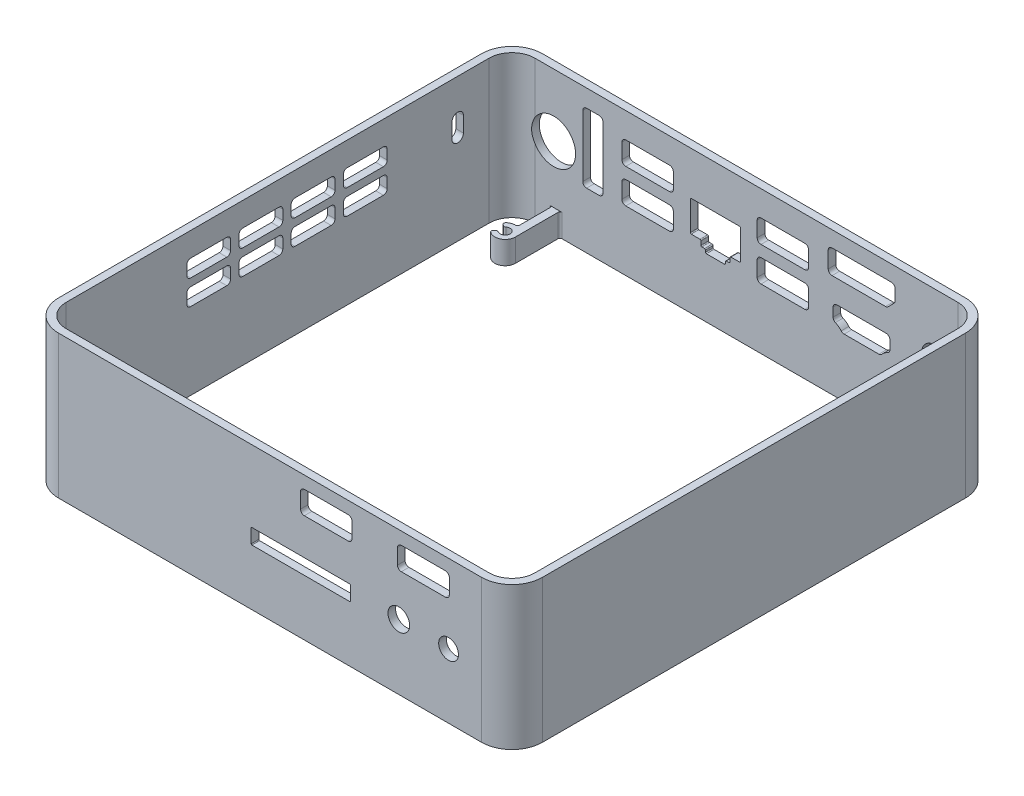
SolidWorks part; units mm, degrees
ref_plane "Front Plane" through (0, 0, 0) normal (0, 0, 1) x (1, 0, 0)
ref_plane "Top Plane" through (0, 0, 0) normal (0, 1, 0) x (1, 0, 0)
ref_plane "Right Plane" through (0, 0, 0) normal (1, 0, 0) x (0, 0, -1)
sketch "Sketch1" plane through (0, 0, 0) normal (0, 1, 0) x (1, 0, 0)
  line L0 (2, 8) -> (2, 119)
  line L1 (8, 0) -> (119, 0)
  line L2 (0, 8) -> (0, 119)
  line L3 (8, 127) -> (119, 127)
  line L4 (127, 8) -> (127, 119)
  line L5 (8, 125) -> (119, 125)
  line L6 (125, 8) -> (125, 119)
  line L7 (8, 2) -> (119, 2)
  arc A0 (119, 0) -> (127, 8) centre (119, 8) ccw
  arc A1 (8, 0) -> (0, 8) centre (8, 8) cw
  arc A2 (119, 127) -> (127, 119) centre (119, 119) cw
  arc A3 (0, 119) -> (8, 127) centre (8, 119) cw
  arc A4 (2, 119) -> (8, 125) centre (8, 119) cw
  arc A5 (119, 125) -> (125, 119) centre (119, 119) cw
  arc A6 (119, 2) -> (125, 8) centre (119, 8) ccw
  arc A7 (8, 2) -> (2, 8) centre (8, 8) cw
  point P9 (0, 0)
  dimension "D3" = 8
  dimension "D1" = 127
  dimension "D2" = 127
  dimension "D4" = 2
extrude "Boss-Extrude1" add sketch "Sketch1" along normal blind 37.5
sketch "Sketch12" plane through (0, 0, 0) normal (1, 0, 0) x (0, 0, -1)
  line L1 (40.65, 31.2) -> (50.15, 31.2)
  line L2 (39.65, 30.2) -> (39.65, 27.7)
  line L3 (40.65, 26.7) -> (50.15, 26.7)
  line L4 (51.15, 30.2) -> (51.15, 27.7)
  arc A0 (39.65, 27.7) -> (40.65, 26.7) centre (40.65, 27.7) ccw
  arc A1 (50.15, 26.7) -> (51.15, 27.7) centre (50.15, 27.7) ccw
  arc A2 (50.15, 31.2) -> (51.15, 30.2) centre (50.15, 30.2) cw
  arc A3 (40.65, 31.2) -> (39.65, 30.2) centre (40.65, 30.2) ccw
  dimension "D5" = 1
  dimension "D1" = 39.65
  dimension "D2" = 11.5
  dimension "D3" = 26.7
  dimension "D4" = 4.5
extrude "Cut-Extrude2" cut sketch "Sketch12" along normal up to next
pattern_linear "LPattern1" count 2 spacing 6.5 along (0, -1, 0) count 4 spacing 13.7 along (0, 0, -1) of "Cut-Extrude2"
sketch "Sketch18" plane through (0, 0, 0) normal (-1, 0, 0) x (0, 0, 1)
  line L0 (-110.75, 23.85) -> (-110.75, 27.85) construction
  line L1 (-112.25, 23.85) -> (-112.25, 27.85)
  line L2 (-109.25, 23.85) -> (-109.25, 27.85)
  line L3 (-119, 37.5) -> (-8, 37.5) construction
  line L4 (-127, 37.5) -> (-127, 0) construction
  arc A0 (-112.25, 23.85) -> (-109.25, 23.85) centre (-110.75, 23.85) ccw
  arc A1 (-109.25, 27.85) -> (-112.25, 27.85) centre (-110.75, 27.85) ccw
  point P2 (-110.75, 25.85)
  dimension "D2" = 1.5
  dimension "D1" = 4
  dimension "D3" = 9.65
  dimension "D4" = 16.25
extrude "Cut-Extrude8" cut sketch "Sketch18" against normal up to next
sketch "Sketch15" plane through (0, 0, 0) normal (0, 0, 1) x (1, 0, 0)
  line L0 (0, 37.5) -> (0, 0) construction
  line L1 (84.45, 18.7) -> (58.75, 18.7)
  line L2 (84.65, 18.5) -> (84.65, 14.9)
  line L3 (84.45, 14.7) -> (58.75, 14.7)
  line L4 (58.55, 18.5) -> (58.55, 14.9)
  line L5 (72.5, 34.25) -> (84, 34.25)
  line L6 (71.5, 33.25) -> (71.5, 29.25)
  line L7 (72.5, 28.25) -> (84, 28.25)
  line L8 (85, 33.25) -> (85, 29.25)
  line L9 (97.95, 34.25) -> (109.55, 34.25)
  line L10 (96.95, 33.25) -> (96.95, 29.25)
  line L11 (97.95, 28.25) -> (109.55, 28.25)
  line L12 (110.55, 33.25) -> (110.55, 29.25)
  line L14 (8, 0) -> (119, 0) construction
  line L15 (8, 37.5) -> (119, 37.5) construction
  circle A0 centre (97.3, 17.1) radius 2.85
  circle A1 centre (110.35, 16.9) radius 2.6
  arc A2 (84, 28.25) -> (85, 29.25) centre (84, 29.25) ccw
  arc A3 (84, 34.25) -> (85, 33.25) centre (84, 33.25) cw
  arc A4 (72.5, 34.25) -> (71.5, 33.25) centre (72.5, 33.25) ccw
  arc A5 (71.5, 29.25) -> (72.5, 28.25) centre (72.5, 29.25) ccw
  arc A6 (84.65, 14.9) -> (84.45, 14.7) centre (84.45, 14.9) cw
  arc A7 (84.45, 18.7) -> (84.65, 18.5) centre (84.45, 18.5) cw
  arc A8 (58.75, 14.7) -> (58.55, 14.9) centre (58.75, 14.9) cw
  arc A9 (58.75, 18.7) -> (58.55, 18.5) centre (58.75, 18.5) ccw
  arc A10 (96.95, 29.25) -> (97.95, 28.25) centre (97.95, 29.25) ccw
  arc A11 (109.55, 28.25) -> (110.55, 29.25) centre (109.55, 29.25) ccw
  arc A12 (109.55, 34.25) -> (110.55, 33.25) centre (109.55, 33.25) cw
  arc A13 (97.95, 34.25) -> (96.95, 33.25) centre (97.95, 33.25) ccw
  dimension "D13" = 5.7
  dimension "D14" = 5.2
  dimension "D15" = 1
  dimension "D3" = 1
  dimension "D2" = 0.2
  dimension "D4" = 13.6
  dimension "D5" = 13.5
  dimension "D6" = 6
  dimension "D7" = 6
  dimension "D8" = 26.1
  dimension "D9" = 4
  dimension "D10" = 58.55
  dimension "D11" = 71.5
  dimension "D12" = 96.95
  dimension "D16" = 97.3
  dimension "D17" = 110.35
  dimension "D18" = 16.9
  dimension "D19" = 17.1
  dimension "D20" = 14.7
  dimension "D21" = 3.25
  dimension "D22" = 3.25
extrude "Cut-Extrude5" cut sketch "Sketch15" against normal blind 2
sketch "Sketch16" plane through (0, 0, -127) normal (0, 0, -1) x (-1, 0, 0)
  line L0 (-100.162, 21.0556) -> (-87.262, 21.0556)
  line L1 (-86.262, 20.0556) -> (-86.262, 17.7485)
  line L2 (-89.1527, 15.3556) -> (-98.2712, 15.3556)
  line L3 (-101.162, 17.7485) -> (-101.162, 20.0556)
  line L4 (-101.5483, 33.3493) -> (-85.9787, 33.3493)
  line L5 (-78.8419, 30.8312) -> (-67.3419, 30.8312)
  line L6 (-79.8419, 29.8312) -> (-79.8419, 25.8312)
  line L7 (-78.8419, 24.8312) -> (-67.3419, 24.8312)
  line L8 (-66.3419, 29.8312) -> (-66.3419, 25.8312)
  line L9 (-24.8661, 32.9015) -> (-21.5749, 32.9015)
  line L10 (-25.8661, 31.9015) -> (-25.8661, 15.7374)
  line L11 (-24.8661, 14.7374) -> (-21.5749, 14.7374)
  line L12 (-20.5749, 31.9015) -> (-20.5749, 15.7374)
  line L13 (-84.9787, 32.3493) -> (-84.9787, 28.0682)
  line L14 (-85.9787, 27.0682) -> (-100.024, 27.0682)
  line L15 (-100.7372, 27.3673) -> (-102.2616, 28.9183)
  line L16 (-102.5483, 29.6193) -> (-102.5483, 32.3493)
  line L17 (-61.736, 26.1367) -> (-49.037, 26.1367)
  line L18 (-48.787, 25.8867) -> (-48.787, 18.2544)
  line L19 (-49.037, 18.0044) -> (-51.332, 18.0044)
  line L20 (-51.582, 17.7544) -> (-51.582, 16.7547)
  line L21 (-51.832, 16.5047) -> (-52.5205, 16.5047)
  line L22 (-52.7705, 16.2547) -> (-52.7705, 15.7891)
  line L23 (-53.0205, 15.5391) -> (-57.7525, 15.5391)
  line L24 (-58.0025, 15.7891) -> (-58.0025, 16.2547)
  line L25 (-58.2525, 16.5047) -> (-58.941, 16.5047)
  line L26 (-59.191, 16.7547) -> (-59.191, 17.7544)
  line L27 (-59.441, 18.0044) -> (-61.736, 18.0044)
  line L28 (-61.986, 18.2544) -> (-61.986, 25.8867)
  circle A0 centre (-113.0051, 21.3213) radius 3.5
  arc A1 (-86.866, 16.8303) -> (-88.3931, 15.7052) centre (-85.2027, 12.9737) ccw
  arc A2 (-99.0308, 15.7052) -> (-100.558, 16.8303) centre (-102.2212, 12.9737) ccw
  circle A3 centre (-12.946, 21.0556) radius 5.75
  arc A4 (-21.5749, 14.7374) -> (-20.5749, 15.7374) centre (-21.5749, 15.7374) ccw
  arc A5 (-25.8661, 15.7374) -> (-24.8661, 14.7374) centre (-24.8661, 15.7374) ccw
  arc A6 (-24.8661, 32.9015) -> (-25.8661, 31.9015) centre (-24.8661, 31.9015) ccw
  arc A7 (-67.3419, 30.8312) -> (-66.3419, 29.8312) centre (-67.3419, 29.8312) cw
  arc A8 (-67.3419, 24.8312) -> (-66.3419, 25.8312) centre (-67.3419, 25.8312) ccw
  arc A9 (-79.8419, 25.8312) -> (-78.8419, 24.8312) centre (-78.8419, 25.8312) ccw
  arc A10 (-78.8419, 30.8312) -> (-79.8419, 29.8312) centre (-78.8419, 29.8312) ccw
  arc A11 (-100.558, 16.8303) -> (-101.162, 17.7485) centre (-100.162, 17.7485) cw
  arc A12 (-98.2712, 15.3556) -> (-99.0308, 15.7052) centre (-98.2712, 16.3556) cw
  arc A13 (-88.3931, 15.7052) -> (-89.1527, 15.3556) centre (-89.1527, 16.3556) cw
  arc A14 (-86.262, 17.7485) -> (-86.866, 16.8303) centre (-87.262, 17.7485) cw
  arc A15 (-87.262, 21.0556) -> (-86.262, 20.0556) centre (-87.262, 20.0556) cw
  arc A16 (-100.162, 21.0556) -> (-101.162, 20.0556) centre (-100.162, 20.0556) ccw
  arc A17 (-21.5749, 32.9015) -> (-20.5749, 31.9015) centre (-21.5749, 31.9015) cw
  arc A18 (-100.024, 27.0682) -> (-100.7372, 27.3673) centre (-100.024, 28.0682) cw
  arc A19 (-84.9787, 28.0682) -> (-85.9787, 27.0682) centre (-85.9787, 28.0682) cw
  arc A20 (-85.9787, 33.3493) -> (-84.9787, 32.3493) centre (-85.9787, 32.3493) cw
  arc A21 (-101.5483, 33.3493) -> (-102.5483, 32.3493) centre (-101.5483, 32.3493) ccw
  arc A22 (-102.2616, 28.9183) -> (-102.5483, 29.6193) centre (-101.5483, 29.6193) cw
  arc A23 (-61.736, 18.0044) -> (-61.986, 18.2544) centre (-61.736, 18.2544) cw
  arc A24 (-59.191, 17.7544) -> (-59.441, 18.0044) centre (-59.441, 17.7544) ccw
  arc A25 (-58.941, 16.5047) -> (-59.191, 16.7547) centre (-58.941, 16.7547) cw
  arc A26 (-58.0025, 16.2547) -> (-58.2525, 16.5047) centre (-58.2525, 16.2547) ccw
  arc A27 (-57.7525, 15.5391) -> (-58.0025, 15.7891) centre (-57.7525, 15.7891) cw
  arc A28 (-52.7705, 15.7891) -> (-53.0205, 15.5391) centre (-53.0205, 15.7891) cw
  arc A29 (-52.5205, 16.5047) -> (-52.7705, 16.2547) centre (-52.5205, 16.2547) ccw
  arc A30 (-51.582, 16.7547) -> (-51.832, 16.5047) centre (-51.832, 16.7547) cw
  arc A31 (-51.332, 18.0044) -> (-51.582, 17.7544) centre (-51.332, 17.7544) ccw
  arc A32 (-48.787, 18.2544) -> (-49.037, 18.0044) centre (-49.037, 18.2544) cw
  arc A33 (-49.037, 26.1367) -> (-48.787, 25.8867) centre (-49.037, 25.8867) cw
  arc A34 (-61.736, 26.1367) -> (-61.986, 25.8867) centre (-61.736, 25.8867) ccw
  point P40 (-98.762, 15.3556)
  point P43 (-88.662, 15.3556)
  dimension "D1" = 7
  dimension "D5" = 4.2
  dimension "D6" = 11.5
  dimension "D7" = 1
  dimension "D8" = 1
  dimension "D9" = 0.25
  dimension "D2" = 2.4
  dimension "D3" = 2.4
  dimension "D4" = 5.7
  dimension "D10" = 14.9
  dimension "D11" = 6
  dimension "D12" = 13.5
extrude "Cut-Extrude6" cut sketch "Sketch16" against normal up to next
pattern_linear "LPattern2" count 2 spacing 35.5 along (-1, 0, 0) count 2 spacing 9 along (0, -1, 0) of face at (73.0919, 24.8312, -126) of face at (66.7384, 25.2276, -126) of face at (66.3419, 27.8312, -126) of face at (66.7384, 30.4348, -126) of face at (73.0919, 30.8312, -126) of face at (79.4455, 30.4348, -126) of face at (79.8419, 27.8312, -126) of face at (79.4455, 25.2276, -126)
sketch "Sketch19" plane through (0, 0, 0) normal (0, -1, 0) x (1, 0, 0)
  line L0 (2, -8) -> (2, -119)
  line L1 (8, -125) -> (119, -125)
  line L2 (125, -119) -> (125, -8)
  line L3 (119, -2) -> (8, -2)
  arc A0 (2, -119) -> (8, -125) centre (8, -119) ccw
  arc A1 (2, -119) -> (8, -125) centre (8, -119) ccw construction
  arc A2 (119, -125) -> (125, -119) centre (119, -119) ccw
  arc A3 (125, -8) -> (119, -2) centre (119, -8) ccw
  arc A4 (8, -2) -> (2, -8) centre (8, -8) ccw
extrude "Boss-Extrude2" add sketch "Sketch19" against normal blind 6
sketch "Sketch20" plane through (0, 0, 0) normal (0, -1, 0) x (1, 0, 0)
  line L0 (8, 0) -> (119, 0) construction
  line L1 (0, -119) -> (0, -8) construction
  line L2 (127, -8) -> (127, -119) construction
  line L3 (119, -127) -> (8, -127) construction
  line L21 (5.2875, -11.9366) -> (8.8282, -12.578)
  line L22 (13.5274, -11.7374) -> (12.4243, -12.5995)
  line L23 (12.4345, -14.1873) -> (13.5486, -15.0351)
  line L24 (2, -14.2894) -> (8.7989, -14.124)
  line L25 (125, -119) -> (125, -8)
  line L26 (8, -125) -> (119, -125)
  line L27 (2, -8) -> (2, -119)
  line L28 (119, -2) -> (8, -2)
  line L29 (125, -119) -> (125, -13.6956)
  line L30 (14.6, -125) -> (119, -125)
  line L31 (2, -14.2894) -> (2, -119)
  line L32 (119, -2) -> (8, -2)
  line L33 (125, -13.6956) -> (117.7089, -13.6956)
  line L34 (112.8143, -14.4372) -> (113.9995, -13.692)
  line L35 (114.0075, -12.2954) -> (112.831, -11.5365)
  line L36 (117.5665, -11.9016) -> (125, -11.9016)
  line L37 (125, -11.9016) -> (125, -8)
  line L38 (14.6, -125) -> (14.6, -113.3)
  line L39 (9.8176, -111.5814) -> (10.8973, -112.4725)
  line L40 (10.8349, -114.0454) -> (9.6879, -114.8481)
  line L41 (12.4735, -115.9384) -> (12.4735, -125)
  line L42 (12.4735, -125) -> (8, -125)
  arc A16 (2, -8) -> (5.2875, -11.9366) centre (6.0007, -8) ccw
  arc A17 (8.8282, -12.578) -> (13.5274, -11.7374) centre (11.4, -13.4) cw
  arc A18 (12.4243, -12.5995) -> (12.4345, -14.1873) centre (11.4, -13.4) ccw
  arc A19 (13.5486, -15.0351) -> (8.7989, -14.124) centre (11.4, -13.4) cw
  arc A20 (125, -8) -> (119, -2) centre (119, -8) ccw
  arc A21 (119, -125) -> (125, -119) centre (119, -119) ccw
  arc A22 (2, -119) -> (8, -125) centre (8, -119) ccw
  arc A23 (8, -2) -> (2, -8) centre (8, -8) ccw
  arc A24 (125, -8) -> (119, -2) centre (119, -8) ccw
  arc A25 (119, -125) -> (125, -119) centre (119, -119) ccw
  arc A26 (2, -119) -> (8, -125) centre (8, -119) ccw
  arc A27 (8, -2) -> (2, -8) centre (8, -8) ccw
  arc A28 (117.7089, -13.6956) -> (112.8143, -14.4372) centre (115.1, -13) cw
  arc A29 (113.9995, -13.692) -> (114.0075, -12.2954) centre (115.1, -13) ccw
  arc A30 (112.831, -11.5365) -> (117.5665, -11.9016) centre (115.1, -13) cw
  arc A31 (14.6, -113.3) -> (9.8176, -111.5814) centre (11.9, -113.3) ccw
  arc A32 (10.8973, -112.4725) -> (10.8349, -114.0454) centre (11.9, -113.3) cw
  arc A33 (9.6879, -114.8481) -> (12.4735, -115.9384) centre (11.9, -113.3) ccw
  dimension "D2" = 1.3
  dimension "D3" = 2.7
  dimension "D4" = 13.4
  dimension "D5" = 11.4
  dimension "D6" = 11.9
  dimension "D7" = 13
  dimension "D8" = 11.9
  dimension "D9" = 13.7
  dimension "D1" = 2
extrude "Cut-Extrude9" cut sketch "Sketch20" against normal up to next
fillet "Fillet1" radius 0.5 22 edges at (9.8176, 3, -111.5814) (10.8973, 3, -112.4725) (10.8349, 3, -114.0454) (9.6879, 3, -114.8481) (12.4735, 3, -115.9384) (14.6, 3, -125) (12.4735, 3, -125) (8.8282, 3, -12.578) (12.4243, 3, -12.5995) (12.4345, 3, -14.1873) (13.5274, 3, -11.7374) (13.5486, 3, -15.0351) (8.7989, 3, -14.124) (2, 3, -14.2894) (113.9995, 3, -13.692) (112.8143, 3, -14.4372) (112.831, 3, -11.5365) (114.0075, 3, -12.2954) (125, 3, -11.9016) (125, 3, -13.6956) (117.5665, 3, -11.9016) (117.7089, 3, -13.6956)
